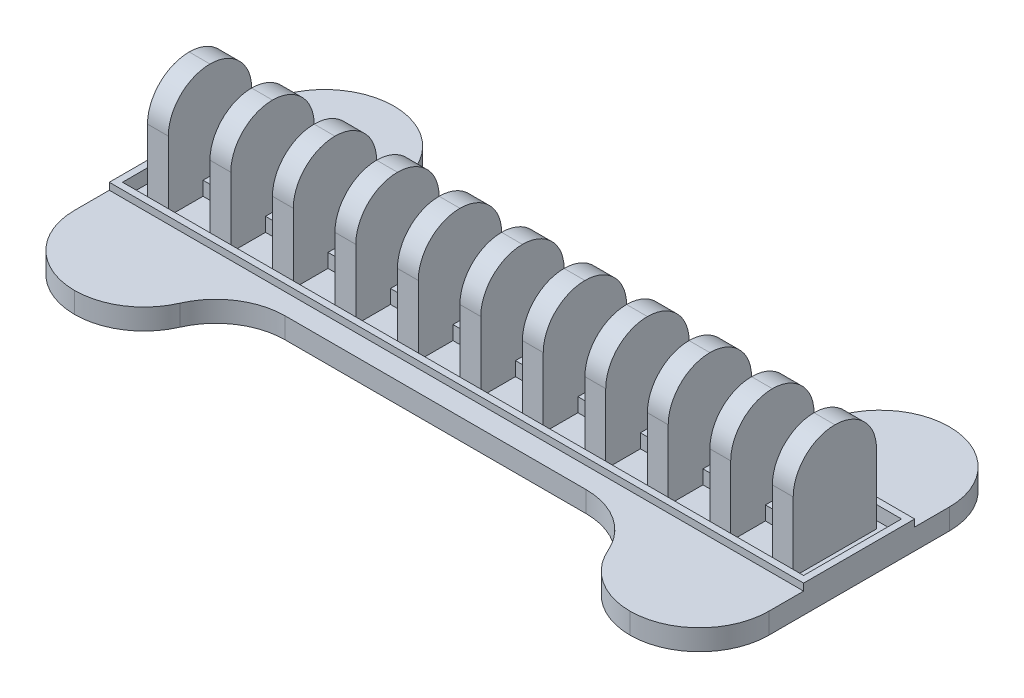
SolidWorks part; units mm, degrees
ref_plane "Front Plane" through (0, 0, 0) normal (0, 0, 1) x (1, 0, 0)
ref_plane "Top Plane" through (0, 0, 0) normal (0, 1, 0) x (1, 0, 0)
ref_plane "Right Plane" through (0, 0, 0) normal (1, 0, 0) x (0, 0, -1)
sketch "Sketch1" plane through (0, 0, 0) normal (0, 1, 0) x (1, 0, 0)
  line L1 (0, 0) -> (100, 0)
  line L2 (0, 0) -> (0, 16)
  line L3 (0, 16) -> (100, 16)
  line L4 (100, 0) -> (100, 16)
  dimension "D1" = 16
  dimension "D2" = 100
extrude "Boss-Extrude1" add sketch "Sketch1" along normal blind 3
sketch "Sketch2" plane through (0, 3, 0) normal (0, 1, 0) x (1, 0, 0)
  line L0 (0, 16) -> (0, 0) construction
  line L1 (1, 1) -> (99, 1)
  line L2 (1, 1) -> (1, 15)
  line L3 (1, 15) -> (99, 15)
  line L4 (99, 1) -> (99, 15)
  line L5 (100, 16) -> (0, 16) construction
  line L6 (0, 0) -> (100, 0) construction
  line L7 (100, 0) -> (100, 16) construction
  dimension "D1" = 1
  dimension "D2" = 1
  dimension "D3" = 1
  dimension "D4" = 1
extrude "Cut-Extrude1" cut sketch "Sketch2" against normal blind 1
sketch "Sketch5" plane through (0, 0, 0) normal (0, 0, 1) x (1, 0, 0)
  line L0 (0, 0) -> (100, 0) construction
  line L1 (0, 3) -> (20, 3)
  line L2 (0, 3) -> (0, 0)
  line L3 (0, 0) -> (20, 0)
  line L4 (20, 3) -> (20, 0)
  line L6 (100, 3) -> (80, 3)
  line L7 (100, 3) -> (100, 0)
  line L8 (100, 0) -> (80, 0)
  line L9 (80, 3) -> (80, 0)
  dimension "D1" = 20
  dimension "D2" = 20
extrude "Boss-Extrude4" add sketch "Sketch5" along normal blind 15
sketch "Sketch6" plane through (0, 0, -16) normal (0, 0, -1) x (-1, 0, 0)
  line L0 (-100, 0) -> (0, 0) construction
  line L1 (-100, 3) -> (-80, 3)
  line L2 (-100, 3) -> (-100, 0)
  line L3 (-100, 0) -> (-80, 0)
  line L4 (-80, 3) -> (-80, 0)
  line L6 (0, 3) -> (-20, 3)
  line L7 (0, 3) -> (0, 0)
  line L8 (0, 0) -> (-20, 0)
  line L9 (-20, 3) -> (-20, 0)
  dimension "D1" = 20
  dimension "D2" = 20
extrude "Boss-Extrude5" add sketch "Sketch6" along normal blind 15
fillet "Fillet18" radius 10 8 edges at (20, 1.5, 15) (0, 1.5, 15) (80, 1.5, 15) (100, 1.5, 15) (0, 1.5, -31) (20, 1.5, -31) (80, 1.5, -31) (100, 1.5, -31)
sketch "Sketch7" plane through (0, 2, 0) normal (0, 1, 0) x (1, 0, 0)
  line L0 (99, 1) -> (99, 15) construction
  line L1 (96.5, 2) -> (93.5, 2)
  line L2 (96.5, 2) -> (96.5, 14)
  line L3 (96.5, 14) -> (93.5, 14)
  line L4 (93.5, 2) -> (93.5, 14)
  line L5 (1, 1) -> (99, 1) construction
  line L6 (87.5, 2) -> (87.5, 14)
  line L7 (87.5, 2) -> (84.5, 2)
  line L8 (84.5, 2) -> (84.5, 14)
  line L9 (87.5, 14) -> (84.5, 14)
  line L10 (78.5, 2) -> (78.5, 14)
  line L11 (78.5, 2) -> (75.5, 2)
  line L12 (75.5, 2) -> (75.5, 14)
  line L13 (78.5, 14) -> (75.5, 14)
  line L14 (69.5, 2) -> (69.5, 14)
  line L15 (69.5, 2) -> (66.5, 2)
  line L16 (66.5, 2) -> (66.5, 14)
  line L17 (69.5, 14) -> (66.5, 14)
  line L18 (60.5, 2) -> (60.5, 14)
  line L19 (60.5, 2) -> (57.5, 2)
  line L20 (57.5, 2) -> (57.5, 14)
  line L21 (60.5, 14) -> (57.5, 14)
  line L22 (51.5, 2) -> (51.5, 14)
  line L23 (51.5, 2) -> (48.5, 2)
  line L24 (48.5, 2) -> (48.5, 14)
  line L25 (51.5, 14) -> (48.5, 14)
  line L26 (42.5, 2) -> (42.5, 14)
  line L27 (42.5, 2) -> (39.5, 2)
  line L28 (39.5, 2) -> (39.5, 14)
  line L29 (42.5, 14) -> (39.5, 14)
  line L30 (33.5, 2) -> (33.5, 14)
  line L31 (33.5, 2) -> (30.5, 2)
  line L32 (30.5, 2) -> (30.5, 14)
  line L33 (33.5, 14) -> (30.5, 14)
  line L34 (24.5, 2) -> (24.5, 14)
  line L35 (24.5, 2) -> (21.5, 2)
  line L36 (21.5, 2) -> (21.5, 14)
  line L37 (24.5, 14) -> (21.5, 14)
  line L38 (15.5, 2) -> (15.5, 14)
  line L39 (15.5, 2) -> (12.5, 2)
  line L40 (12.5, 2) -> (12.5, 14)
  line L41 (15.5, 14) -> (12.5, 14)
  line L42 (6.5, 2) -> (6.5, 14)
  line L43 (6.5, 2) -> (3.5, 2)
  line L44 (3.5, 2) -> (3.5, 14)
  line L45 (6.5, 14) -> (3.5, 14)
  line L46 (96.5, 2) -> (87.5, 2) construction
  dimension "D1" = 12
  dimension "D2" = 3
  dimension "D3" = 2.5
  dimension "D4" = 1
  dimension "D6" = 9
  dimension "D5" = 11
extrude "Boss-Extrude6" add sketch "Sketch7" along normal blind 16
sketch "Sketch8" plane through (0, 2, 0) normal (0, 1, 0) x (1, 0, 0)
  line L0 (93.5, 14) -> (93.5, 2) construction
  line L1 (93.5, 7) -> (87.5, 7)
  line L2 (93.5, 7) -> (93.5, 9)
  line L3 (93.5, 9) -> (87.5, 9)
  line L4 (87.5, 7) -> (87.5, 9)
  line L5 (87.5, 2) -> (87.5, 14) construction
  line L6 (99, 15) -> (1, 15) construction
  line L8 (84.5, 7) -> (84.5, 9)
  line L9 (84.5, 7) -> (78.5, 7)
  line L10 (78.5, 7) -> (78.5, 9)
  line L11 (84.5, 9) -> (78.5, 9)
  line L12 (75.5, 7) -> (75.5, 9)
  line L13 (75.5, 7) -> (69.5, 7)
  line L14 (69.5, 7) -> (69.5, 9)
  line L15 (75.5, 9) -> (69.5, 9)
  line L16 (66.5, 7) -> (66.5, 9)
  line L17 (66.5, 7) -> (60.5, 7)
  line L18 (60.5, 7) -> (60.5, 9)
  line L19 (66.5, 9) -> (60.5, 9)
  line L20 (57.5, 7) -> (57.5, 9)
  line L21 (57.5, 7) -> (51.5, 7)
  line L22 (51.5, 7) -> (51.5, 9)
  line L23 (57.5, 9) -> (51.5, 9)
  line L24 (48.5, 7) -> (48.5, 9)
  line L25 (48.5, 7) -> (42.5, 7)
  line L26 (42.5, 7) -> (42.5, 9)
  line L27 (48.5, 9) -> (42.5, 9)
  line L28 (39.5, 7) -> (39.5, 9)
  line L29 (39.5, 7) -> (33.5, 7)
  line L30 (33.5, 7) -> (33.5, 9)
  line L31 (39.5, 9) -> (33.5, 9)
  line L32 (30.5, 7) -> (30.5, 9)
  line L33 (30.5, 7) -> (24.5, 7)
  line L34 (24.5, 7) -> (24.5, 9)
  line L35 (30.5, 9) -> (24.5, 9)
  line L36 (21.5, 7) -> (21.5, 9)
  line L37 (21.5, 7) -> (15.5, 7)
  line L38 (15.5, 7) -> (15.5, 9)
  line L39 (21.5, 9) -> (15.5, 9)
  line L40 (12.5, 7) -> (12.5, 9)
  line L41 (12.5, 7) -> (6.5, 7)
  line L42 (6.5, 7) -> (6.5, 9)
  line L43 (12.5, 9) -> (6.5, 9)
  line L44 (93.5, 7) -> (84.5, 7) construction
  dimension "D1" = 2
  dimension "D2" = 6
  dimension "D3" = 10
  dimension "D4" = 9
extrude "Boss-Extrude7" add sketch "Sketch8" along normal blind 2
fillet "Fillet19" radius 6 22 edges at (95, 18, -2) (95, 18, -14) (86, 18, -2) (86, 18, -14) (77, 18, -2) (77, 18, -14) (68, 18, -2) (68, 18, -14) (59, 18, -2) (59, 18, -14) (50, 18, -2) (50, 18, -14) (41, 18, -2) (41, 18, -14) (32, 18, -2) (32, 18, -14) (23, 18, -14) (23, 18, -2) (14, 18, -2) (14, 18, -14) (5, 18, -2) (5, 18, -14)
sketch "Sketch10" plane through (0, 0, -16) normal (0, 0, -1) x (-1, 0, 0)
  line L1 (-80, 3) -> (-20, 3)
  line L2 (-80, 3) -> (-80, 0)
  line L3 (-80, 0) -> (-20, 0)
  line L4 (-20, 3) -> (-20, 0)
extrude "Boss-Extrude8" add sketch "Sketch10" along normal blind 3
sketch "Sketch11" plane through (0, 0, 0) normal (0, 0, 1) x (1, 0, 0)
  line L1 (20, 3) -> (80, 3)
  line L2 (20, 3) -> (20, 0)
  line L3 (20, 0) -> (80, 0)
  line L4 (80, 3) -> (80, 0)
extrude "Boss-Extrude9" add sketch "Sketch11" along normal blind 3
sketch "Sketch12" plane through (0, 3, 0) normal (0, 1, 0) x (1, 0, 0)
  line L0 (100, -5) -> (100, 21) construction
  line L1 (100, 14.9979) -> (99.05, 14.9979)
  line L2 (100, 14.9979) -> (100, 0.9979)
  line L3 (100, 0.9979) -> (99.05, 0.9979)
  line L4 (99.05, 14.9979) -> (99.05, 0.9979)
  line L5 (0, 21) -> (0, -5) construction
  line L6 (0, 14.9979) -> (0.95, 14.9979)
  line L7 (0, 14.9979) -> (0, 0.9979)
  line L8 (0, 0.9979) -> (0.95, 0.9979)
  line L9 (0.95, 14.9979) -> (0.95, 0.9979)
  dimension "D1" = 0.95
  dimension "D2" = 14
  dimension "D3" = 0.95
  dimension "D4" = 14
extrude "Boss-Extrude10" add sketch "Sketch12" along normal blind 3
sketch "Sketch13" plane through (0, 3, 0) normal (0, 1, 0) x (1, 0, 0)
  line L0 (0, 21) -> (0, 14.9979) construction
  line L1 (0, 15.05) -> (100, 15.05)
  line L2 (0, 15.05) -> (0, 16)
  line L3 (0, 16) -> (100, 16)
  line L4 (100, 15.05) -> (100, 16)
  line L5 (100, 14.9979) -> (100, 21) construction
  line L6 (100, -5) -> (100, 0.9979) construction
  line L7 (0, 0) -> (100, 0)
  line L8 (0, 0) -> (0, 0.95)
  line L9 (0, 0.95) -> (100, 0.95)
  line L10 (100, 0) -> (100, 0.95)
  line L11 (99, 15) -> (1, 15) construction
  line L13 (1, 1) -> (99, 1) construction
  dimension "D1" = 0.95
  dimension "D2" = 0.05
  dimension "D3" = 0.05
extrude "Boss-Extrude11" add sketch "Sketch13" along normal blind 3
sketch "Sketch14" plane through (0, 3, 0) normal (0, 1, 0) x (1, 0, 0)
  line L0 (0.95, 14.9979) -> (0, 14.9979) construction
  line L1 (0, 15.05) -> (0.95, 15.05)
  line L2 (0, 15.05) -> (0, 14.9979)
  line L3 (0, 14.9979) -> (0.95, 14.9979)
  line L4 (0.95, 15.05) -> (0.95, 14.9979)
  line L5 (0.95, 14.9979) -> (0, 14.9979) construction
extrude "Boss-Extrude12" add sketch "Sketch14" along normal blind 3
sketch "Sketch15" plane through (0, 3, 0) normal (0, 1, 0) x (1, 0, 0)
  line L0 (100, 0.95) -> (0, 0.95) construction
  line L1 (0, 0.9979) -> (0.95, 0.9979)
  line L2 (0, 0.9979) -> (0, 0.95)
  line L3 (0, 0.95) -> (0.95, 0.95)
  line L4 (0.95, 0.9979) -> (0.95, 0.95)
  line L6 (100, 0.9979) -> (99.0503, 0.9979)
  line L7 (100, 0.9979) -> (100, 0.95)
  line L8 (100, 0.95) -> (99.0503, 0.95)
  line L9 (99.0503, 0.9979) -> (99.0503, 0.95)
  line L10 (100, 15.05) -> (99.05, 15.05)
  line L11 (100, 15.05) -> (100, 14.9979)
  line L12 (100, 14.9979) -> (99.05, 14.9979)
  line L13 (99.05, 15.05) -> (99.05, 14.9979)
extrude "Boss-Extrude13" add sketch "Sketch15" along normal blind 3
ref_plane "Plane1" through (0, 6, 0) normal (0, 0, 1) x (1, 0, 0)
fillet "Fillet20" radius 10 4 edges at (20, 1.5, -19) (80, 1.5, -19) (80, 1.5, 3) (20, 1.5, 3)
sketch "Sketch17" plane through (0, 6, 0) normal (0, 1, 0) x (1, 0, 0)
  line L0 (0.95, 15.05) -> (0.95, 0.95)
  line L1 (0.95, 15.05) -> (99.05, 15.05)
  line L2 (0.95, 0.95) -> (99.05, 0.95)
  line L3 (99.05, 15.05) -> (99.05, 0.95)
  line L4 (99.05, 15.05) -> (99.05, 0.9979) construction
  line L5 (1.45, 14.55) -> (1.45, 1.45)
  line L6 (1.45, 1.45) -> (98.55, 1.45)
  line L7 (98.55, 14.55) -> (98.55, 1.45)
  line L8 (1.45, 14.55) -> (98.55, 14.55)
  dimension "D1" = 0.5
extrude "Cut-Extrude2" cut sketch "Sketch17" against normal blind 4
sketch "Sketch18" plane through (0, 6, 0) normal (0, 1, 0) x (1, 0, 0)
  line L0 (100, 16) -> (0, 16)
  line L1 (100, 16) -> (100, -0.05)
  line L2 (0, 16) -> (0, -0.05)
  line L3 (100, -0.05) -> (0, -0.05)
  line L4 (99, 15) -> (1, 15)
  line L5 (1, 15) -> (1, 0.95)
  line L6 (99, 0.95) -> (1, 0.95)
  line L7 (99, 15) -> (99, 0.95)
  line L8 (99.0503, 0.95) -> (0.95, 0.95) construction
  dimension "D1" = 1
extrude "Cut-Extrude3" cut sketch "Sketch18" against normal blind 2
